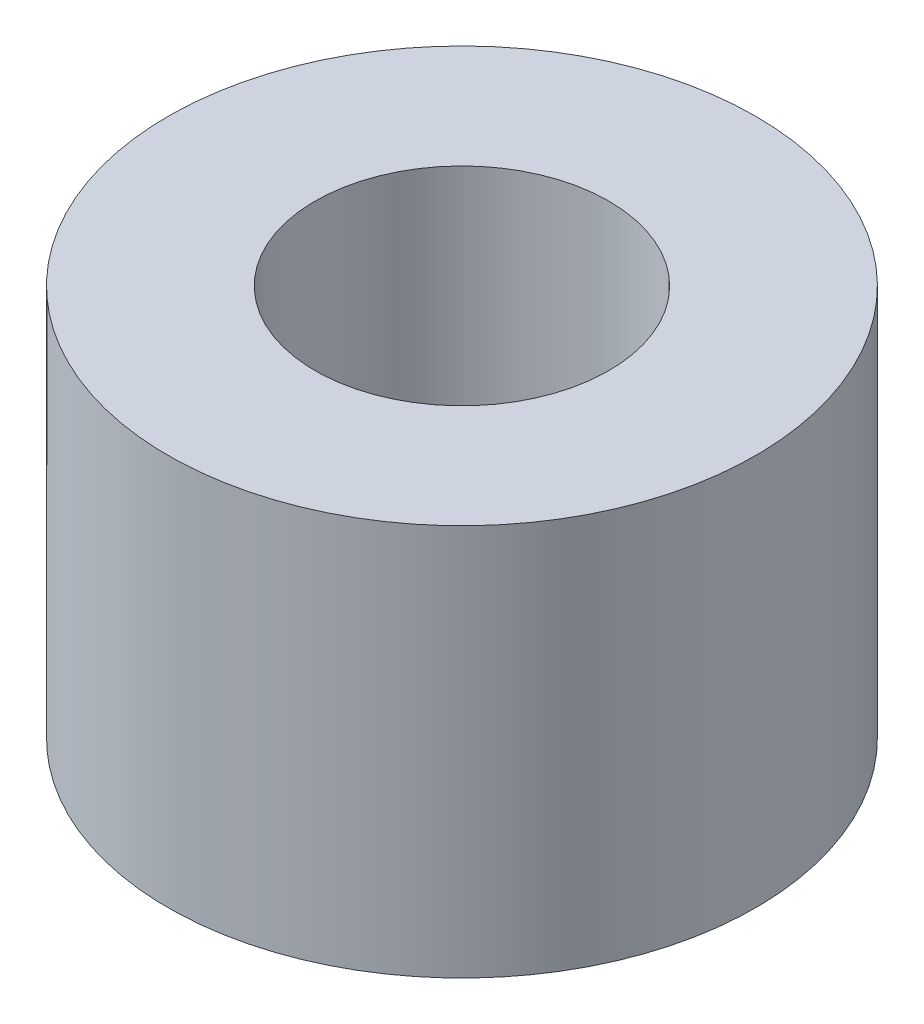
SolidWorks part; units mm, degrees
ref_plane "Front Plane" through (0, 0, 0) normal (0, 0, 1) x (1, 0, 0)
ref_plane "Top Plane" through (0, 0, 0) normal (0, 1, 0) x (1, 0, 0)
ref_plane "Right Plane" through (0, 0, 0) normal (1, 0, 0) x (0, 0, -1)
sketch "Sketch4" plane through (0, 0, 0) normal (0, 1, 0) x (1, 0, 0)
  circle A0 centre (0, 0) radius 28.575
  circle A1 centre (0, 0) radius 14.2875
  dimension "D1" = 57.15
  dimension "D2" = 28.575
extrude "Boss-Extrude1" add sketch "Sketch4" along normal mid plane 38.1
sketch "Sketch5" plane through (0, 0, 0) normal (0, 1, 0) x (1, 0, 0)
  line L0 (0, 0) -> (82.55, 0) construction
  line L1 (4.3962, 28.2348) -> (84.9923, 15.686)
  line L2 (4.3962, -28.2348) -> (84.9923, -15.686)
  circle A0 centre (0, 0) radius 28.575 construction
  circle A1 centre (0, 0) radius 28.575
  circle A2 centre (82.55, 0) radius 15.875
  circle A3 centre (82.55, 0) radius 6.35
  dimension "D1" = 31.75
  dimension "D2" = 12.7
  dimension "D3" = 82.55
